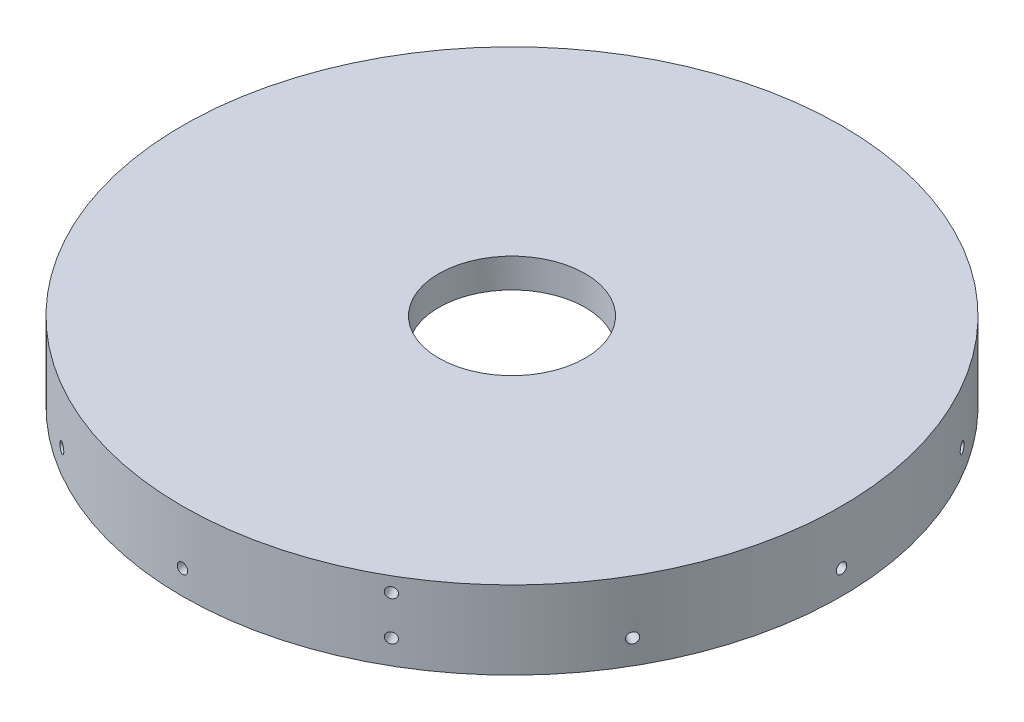
SolidWorks part; units mm, degrees
material "6061-T6 (SS)"
ref_plane "Front Plane" through (0, 0, 0) normal (0, 0, 1) x (1, 0, 0)
ref_plane "Top Plane" through (0, 0, 0) normal (0, 1, 0) x (1, 0, 0)
ref_plane "Right Plane" through (0, 0, 0) normal (1, 0, 0) x (0, 0, -1)
sketch "Sketch1" plane through (0, 0, 0) normal (0, 1, 0) x (1, 0, 0)
  circle A0 centre (0, 0) radius 85.725
  dimension "D1" = 171.45
extrude "Boss-Extrude1" add sketch "Sketch1" along normal mid plane 7.62
sketch "Sketch2" plane through (0, -3.81, 0) normal (0, -1, 0) x (1, 0, 0)
  circle A0 centre (0, 0) radius 19.05
  dimension "D1" = 38.1
extrude "Cut-Extrude1" cut sketch "Sketch2" against normal up to surface (7.62 mm away) up to face at (0, 3.81, 85.725)
sketch "Sketch4" plane through (0, -3.81, 0) normal (0, -1, 0) x (1, 0, 0)
  circle A0 centre (0, 0) radius 85.725
  circle A1 centre (0, 0) radius 79.375
  dimension "D1" = 171.45
  dimension "D2" = 158.75
extrude "Boss-Extrude2" add sketch "Sketch4" along normal blind 12.7
ref_plane "Plane1" through (-85.725, 0, 0) normal (-1, 0, 0) x (0, 0, 1)
sketch "Sketch3" plane through (-85.725, 0, 0) normal (-1, 0, 0) x (0, 0, 1)
  circle A0 centre (0, 0) radius 1.3525
  dimension "D1" = 2.7051
extrude "Cut-Extrude2" cut sketch "Sketch3" against normal blind 15.24
pattern_circular "CirPattern1" count 3 over 360 about axis through (0, 3.81, 0) along (0, -1, 0) of "Cut-Extrude2" reverse direction yes
sketch "Sketch5" plane through (-85.725, 0, 0) normal (-1, 0, 0) x (0, 0, 1)
  line L0 (0, -11.176) -> (0, 11.176) construction
  line L1 (-79.375, -16.51) -> (79.375, -16.51) construction
  circle A0 centre (0, -10.1828) radius 1.3525
  dimension "D1" = 2.7051
  dimension "D2" = 6.3272
extrude "Cut-Extrude3" cut sketch "Sketch5" against normal blind 17.018
pattern_circular "CirPattern2" count 12 over 360 about axis through (0, 3.81, 0) along (0, -1, 0) of "Cut-Extrude3"
